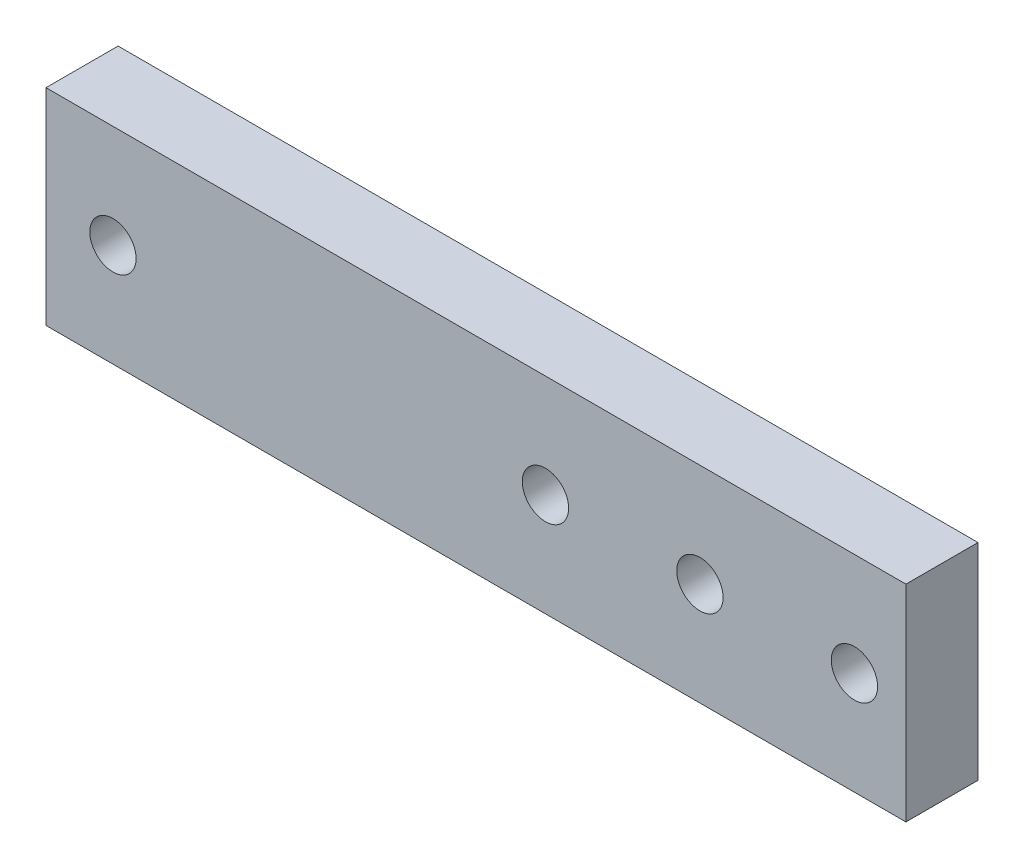
SolidWorks part; units mm, degrees
ref_plane "Front Plane" through (0, 0, 0) normal (0, 0, 1) x (1, 0, 0)
ref_plane "Top Plane" through (0, 0, 0) normal (0, 1, 0) x (1, 0, 0)
ref_plane "Right Plane" through (0, 0, 0) normal (1, 0, 0) x (0, 0, -1)
sketch "Sketch1" plane through (0, 0, 0) normal (0, 0, 1) x (1, 0, 0)
  line L0 (-14.25, 10) -> (-14.25, -10) construction
  line L1 (-41.75, -10) -> (41.75, -10)
  line L2 (-41.75, -10) -> (-41.75, 10)
  line L3 (-41.75, 10) -> (41.75, 10)
  line L4 (41.75, -10) -> (41.75, 10)
  line L5 (-41.75, -10) -> (41.75, 10) construction
  line L6 (-41.75, 10) -> (41.75, -10) construction
  circle A0 centre (6.75, 0) radius 2.25
  circle A1 centre (-35.25, 0) radius 2.25
  circle A2 centre (21.75, 0) radius 2.25
  circle A3 centre (36.75, 0) radius 2.25
  point P0 (0, 0)
  point P10 (0, 0)
  dimension "D1" = 42
  dimension "D2" = 4.5
  dimension "D4" = 15
  dimension "D5" = 15
  dimension "D6" = 6.5
  dimension "D7" = 5
  dimension "D3" = 20
extrude "Boss-Extrude1" add sketch "Sketch1" along normal blind 7
